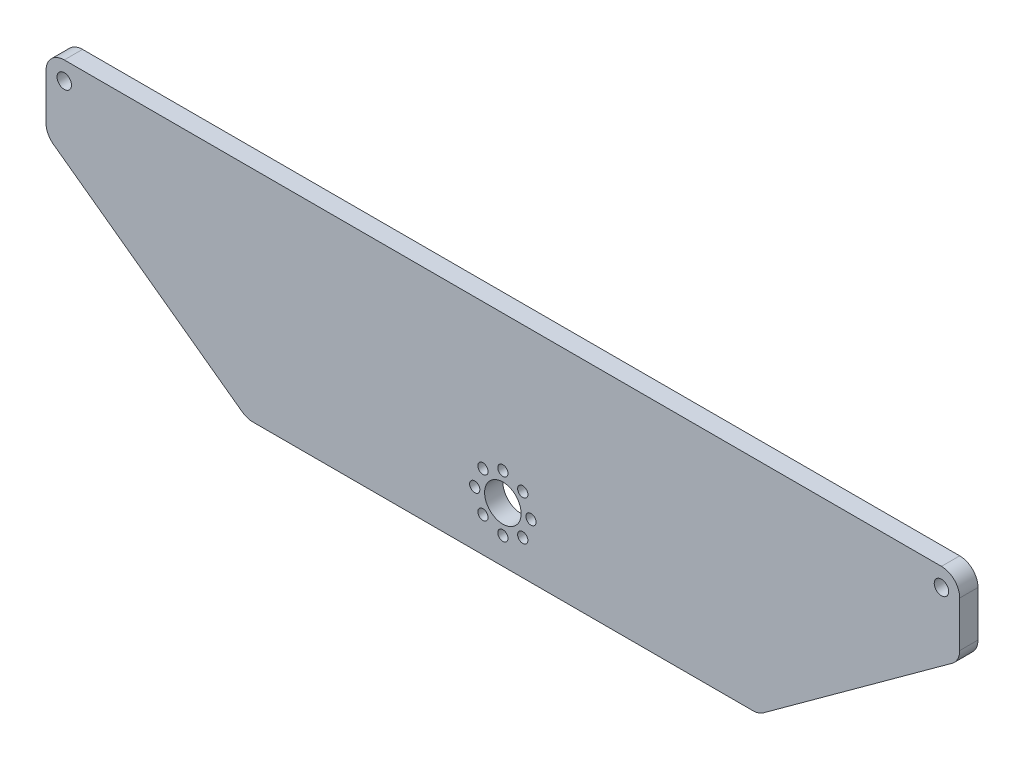
SolidWorks part; units mm, degrees
material "6061-T6 (SS)"
ref_plane "Front Plane" through (0, 0, 0) normal (0, 0, 1) x (1, 0, 0)
ref_plane "Top Plane" through (0, 0, 0) normal (0, 1, 0) x (1, 0, 0)
ref_plane "Right Plane" through (0, 0, 0) normal (1, 0, 0) x (0, 0, -1)
sketch "Sketch1" plane through (0, 0, 0) normal (0, 0, 1) x (1, 0, 0)
  line L1 (158.75, 38.1) -> (-158.75, 38.1)
  line L2 (158.75, 38.1) -> (158.75, -38.1)
  line L3 (158.75, -38.1) -> (-158.75, -38.1)
  line L4 (-158.75, 38.1) -> (-158.75, -38.1)
  line L5 (158.75, 38.1) -> (-158.75, -38.1) construction
  line L6 (158.75, -38.1) -> (-158.75, 38.1) construction
  circle A0 centre (0, -19.05) radius 6.35
  circle A2 centre (152.4, 31.75) radius 2.5083
  circle A4 centre (-152.4, 31.75) radius 2.5083
  point P0 (0, 0)
  point P16 (0, 0)
  point P17 (0, 0)
  dimension "D3" = 12.7
  dimension "D4" = 152.4
  dimension "D9" = 5.0165
  dimension "D10" = 19.05
  dimension "D12" = 5.0165
  dimension "D1" = 317.5
  dimension "D2" = 76.2
  dimension "D6" = 50.8
  dimension "D14" = 152.4
extrude "Boss-Extrude1" add sketch "Sketch1" along normal blind 6.35
sketch "Sketch2" plane through (0, 0, 0) normal (0, 0, -1) x (-1, 0, 0)
  line L0 (88.9, -38.1) -> (158.75, 12.7)
  line L1 (158.75, -38.1) -> (-158.75, -38.1) construction
  line L2 (158.75, 38.1) -> (158.75, -38.1) construction
  line L3 (158.75, 12.7) -> (158.75, -38.1)
  line L4 (158.75, -38.1) -> (88.9, -38.1)
  line L5 (-158.75, -38.1) -> (-158.75, 12.7)
  line L6 (-158.75, -38.1) -> (-158.75, 38.1) construction
  line L7 (-158.75, 12.7) -> (-88.9, -38.1)
  line L8 (-88.9, -38.1) -> (-158.75, -38.1)
  dimension "D1" = 69.85
  dimension "D2" = 69.85
  dimension "D3" = 50.8
  dimension "D4" = 50.8
extrude "Cut-Extrude1" cut sketch "Sketch2" against normal blind 6.35
fillet "Fillet1" radius 6.35 6 edges at (-158.75, 38.1, 3.175) (158.75, 12.7, 3.175) (-158.75, 12.7, 3.175) (-88.9, -38.1, 3.175) (88.9, -38.1, 3.175) (158.75, 38.1, 3.175)
sketch "Sketch3" plane through (0, 0, 0) normal (0, 0, -1) x (-1, 0, 0)
  circle A0 centre (0, -9.271) radius 1.778
  circle A1 centre (0, -19.05) radius 6.35 construction
  dimension "D1" = 3.556
  dimension "D2" = 9.779
extrude "Cut-Extrude2" cut sketch "Sketch3" against normal blind 6.35
pattern_circular "CirPattern1" count 8 over 360 about axis through (0, -19.05, 0) along (0, 0, 1) of "Cut-Extrude2"
